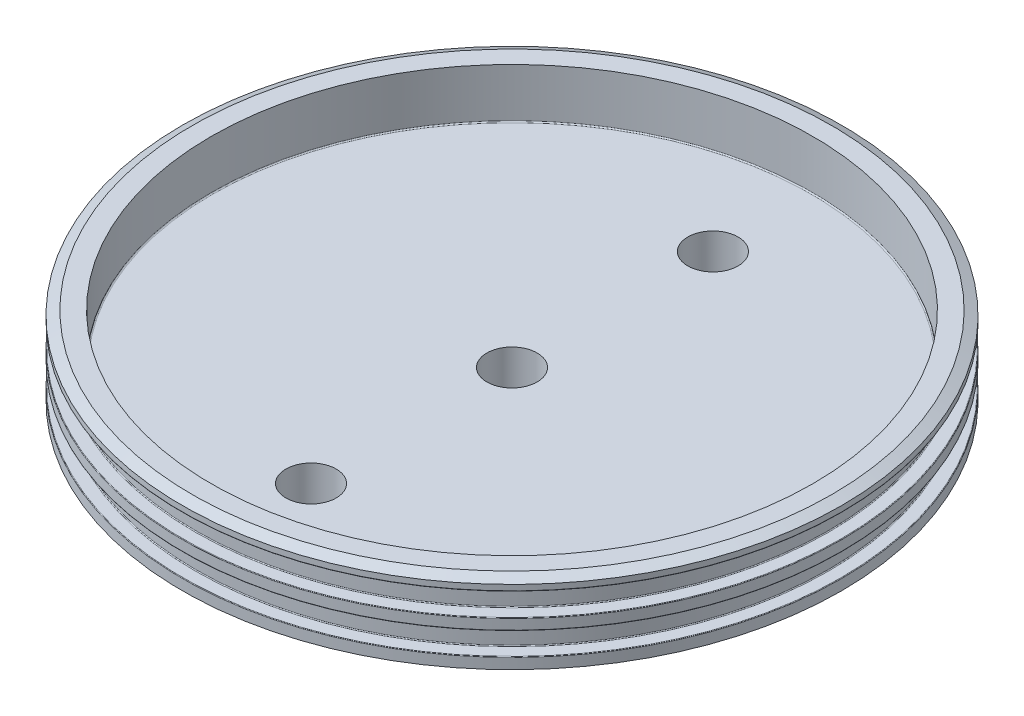
SolidWorks part; units mm, degrees
material "6061-T6 (SS)"
ref_plane "Front Plane" through (0, 0, 0) normal (0, 0, 1) x (1, 0, 0)
ref_plane "Top Plane" through (0, 0, 0) normal (0, 1, 0) x (1, 0, 0)
ref_plane "Right Plane" through (0, 0, 0) normal (1, 0, 0) x (0, 0, -1)
sketch "Sketch1" plane through (0, 0, 0) normal (0, 0, 1) x (1, 0, 0)
  line L0 (0, 48.1922) -> (0, -25.6743) construction
  line L1 (0, 0) -> (72.898, 0)
  line L2 (72.898, 0) -> (72.898, 2.4638)
  line L3 (72.898, 2.4638) -> (69.977, 2.4638)
  line L4 (69.977, 2.4638) -> (69.977, 7.4422)
  line L5 (69.977, 7.4422) -> (72.898, 7.4422)
  line L6 (72.898, 7.4422) -> (72.898, 9.906)
  line L7 (72.898, 9.906) -> (69.977, 9.906)
  line L8 (66.548, 17.3482) -> (66.548, 6.35)
  line L9 (66.548, 6.35) -> (0, 6.35)
  line L10 (0, 6.35) -> (0, 0)
  line L11 (69.977, 9.906) -> (69.977, 14.986)
  line L12 (69.977, 14.986) -> (72.898, 14.986)
  line L13 (72.898, 14.986) -> (72.898, 17.3482)
  line L14 (72.898, 17.3482) -> (66.548, 17.3482)
  dimension "D1" = 145.796
  dimension "D2" = 4.9784
  dimension "D3" = 2.921
  dimension "D4" = 9.906
  dimension "D5" = 6.35
  dimension "D6" = 6.35
  dimension "D7" = 5.08
  dimension "D8" = 9.906
revolve "Revolve1" add sketch "Sketch1" angle 360 about L0
sketch "Sketch6" plane through (0, 0, 0) normal (0, -1, 0) x (1, 0, 0)
  circle A0 centre (0, 0) radius 66.04
  dimension "D1" = 132.08
extrude "Boss-Extrude1" add sketch "Sketch6" along normal blind 2.54
hole_wizard "Pipe Tap Drill for 1/4 Tap - GN2" positions "Sketch2" profile "Sketch3" hole size "1/4" standard "ANSI Inch" end condition through all
sketch "Sketch2" plane through (0, 6.35, 0) normal (0, 1, 0) x (1, 0, 0)
  point P4 (0, 0)
  dimension "D1" = 0
sketch "Sketch3" plane through (0, 6.35, 0) normal (1, 0, 0) x (0, 0, 1)
  line L0 (0, 0) -> (0, 8.89)
  line L1 (0, 8.89) -> (5.5626, 8.89)
  line L2 (5.5626, 8.89) -> (5.5626, 0)
  line L5 (5.5626, 0) -> (0, 0)
  line L11 (0, -6.35) -> (0, 107.95) construction
  dimension "Thru Hole Dia." = 11.1252
  dimension "Thru Hole Depth" = 8.89
fillet "CNC ID Fillet" radius 0.1778 5 edges at (-69.977, 7.4422, 0) (-69.977, 2.4638, 0) (-69.977, 14.986, 0) (-69.977, 9.906, 0) (66.04, 0, 0)
fillet "CNC OD Fillet" radius 0.127 5 edges at (-72.898, 7.4422, 0) (-72.898, 2.4638, 0) (66.04, -2.54, 0) (-72.898, 14.986, 0) (-72.898, 9.906, 0)
chamfer "CNC Chamfers" distance 1.016 angle 65 1 edges at (-72.898, 17.3482, 0) first distance on face at (-72.898, 15.113, 0)
fillet "CNC Bore Fillet" radius 0.254 1 edges at (-66.548, 6.35, 0)
hole_wizard "Pipe Tap Drill for 1/4 Tap - Relief Valve" positions "Sketch13" profile "Sketch14" hole size "1/4" standard "ANSI Inch" end condition through all
sketch "Sketch13" plane through (0, -2.54, 0) normal (0, -1, 0) x (-1, 0, 0)
  point P4 (0, 44.45)
  dimension "D1" = 44.45
sketch "Sketch14" plane through (0, -2.54, -44.45) normal (1, 0, 0) x (0, 0, -1)
  line L0 (0, 0) -> (0, 19.8882)
  line L1 (0, 19.8882) -> (5.5626, 19.8882)
  line L2 (5.5626, 19.8882) -> (5.5626, 0)
  line L5 (5.5626, 0) -> (0, 0)
  line L11 (0, -6.35) -> (0, 107.95) construction
  dimension "Thru Hole Dia." = 11.1252
  dimension "Thru Hole Depth" = 19.8882
hole_wizard "Pipe Tap Drill for 1/4 Tap - Vent Valve" positions "Sketch15" profile "Sketch16" hole size "1/4" standard "ANSI Inch" end condition through all
sketch "Sketch15" plane through (0, -2.54, 0) normal (0, -1, 0) x (-1, 0, 0)
  point P4 (0, -44.45)
  dimension "D1" = 44.45
sketch "Sketch16" plane through (0, -2.54, 44.45) normal (1, 0, 0) x (0, 0, -1)
  line L0 (0, 0) -> (0, 19.8882)
  line L1 (0, 19.8882) -> (5.5626, 19.8882)
  line L2 (5.5626, 19.8882) -> (5.5626, 0)
  line L5 (5.5626, 0) -> (0, 0)
  line L11 (0, -6.35) -> (0, 107.95) construction
  dimension "Thru Hole Dia." = 11.1252
  dimension "Thru Hole Depth" = 19.8882
